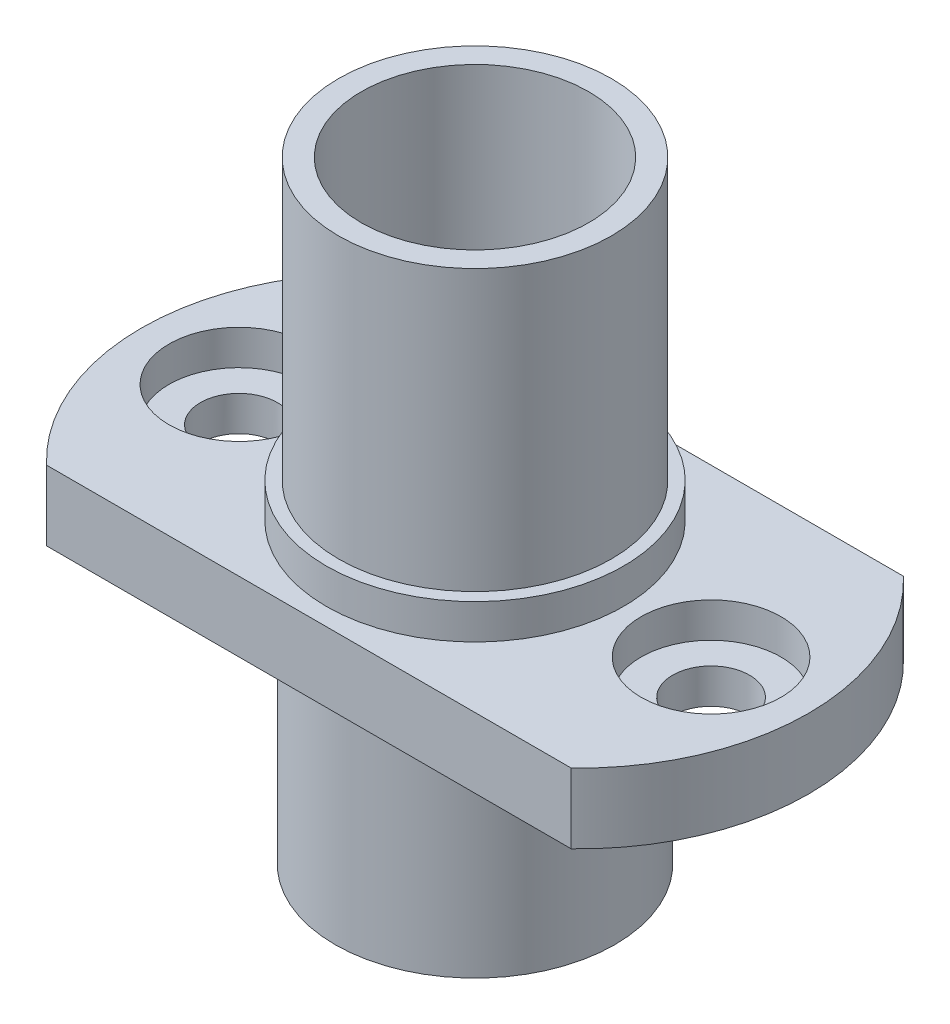
SolidWorks part; units mm, degrees
ref_plane "前视基准面" through (0, 0, 0) normal (0, 0, 1) x (1, 0, 0)
ref_plane "上视基准面" through (0, 0, 0) normal (0, 1, 0) x (1, 0, 0)
ref_plane "右视基准面" through (0, 0, 0) normal (1, 0, 0) x (0, 0, -1)
sketch "草图1" plane through (0, 0, 0) normal (0, 1, 0) x (1, 0, 0)
  line L0 (0, 14.3323) -> (0, -15.2472) construction
  line L1 (-15.1496, 0) -> (19.0046, 0) construction
  line L3 (-7.5, 4.75) -> (7.5, 4.75)
  line L5 (-7.5, -4.75) -> (7.5, -4.75)
  arc A0 (-7.5, -4.75) -> (-7.5, 4.75) centre (-2.99, 0) cw
  arc A1 (7.5, -4.75) -> (7.5, 4.75) centre (2.99, 0) ccw
  dimension "D3" = 6.55
  dimension "D1" = 15
  dimension "D2" = 9.5
extrude "拉伸1" add sketch "草图1" along normal blind 1 and the other way blind 1
sketch "草图2" plane through (0, 1, 0) normal (0, 1, 0) x (-1, 0, 0)
  circle A0 centre (0, 0) radius 4.25
  circle A1 centre (0, 0) radius 3.25
  dimension "D1" = 8.5
  dimension "D2" = 1
extrude "拉伸2" add sketch "草图2" along normal blind 9
sketch "草图3" plane through (0, 1, 0) normal (0, 1, 0) x (-1, 0, 0)
  line L0 (-10.3293, 0) -> (10.9867, 0) construction
  line L1 (0, -7.1957) -> (0, 6.685) construction
  circle A0 centre (-6.75, 0) radius 1.1
  circle A1 centre (6.75, 0) radius 1.1
  dimension "D1" = 13.5
  dimension "D2" = 2.2
extrude "切除-拉伸1" cut sketch "草图3" against normal through all
sketch "草图8" plane through (0, 1, 0) normal (0, 1, 0) x (1, 0, 0)
  circle A0 centre (-6.75, 0) radius 2
  circle A1 centre (6.75, 0) radius 2
  dimension "D1" = 4
  dimension "D2" = 4
extrude "切除-拉伸3" cut sketch "草图8" against normal blind 1
sketch "草图4" plane through (0, -1, 0) normal (0, -1, 0) x (1, 0, 0)
  circle A0 centre (0, 0) radius 4
  dimension "D1" = 8
extrude "凸台-拉伸1" add sketch "草图4" along normal blind 6.5
sketch "草图5" plane through (0, 10, 0) normal (0, 1, 0) x (1, 0, 0)
  circle A0 centre (0, 0) radius 3.9
  dimension "D1" = 7.8
extrude "切除-拉伸2" cut sketch "草图5" against normal offset from surface (8 mm away) 1 flip side to cut up to face at (-6.75, 1, 2)
sketch "草图6" plane through (0, -7.5, 0) normal (0, -1, 0) x (1, 0, 0)
  circle A0 centre (0, 0) radius 0.2
  circle A1 centre (-1.05, 0.1997) radius 0.2
  circle A2 centre (0.756, 0.3) radius 0.2
  dimension "D1" = 0.4
  dimension "D2" = 0.4
  dimension "D3" = 0.4
extrude "凸台-拉伸2" [suppressed] add sketch "草图6" along normal blind 13
sketch "草图7" plane through (0, 0, 0) normal (0, 0, 1) x (1, 0, 0)
  line L0 (0, 0) -> (8.9791, -5.1841) construction
  line L1 (-14.7947, 0) -> (17.5355, 0) construction
  dimension "D1" = 30
ref_plane "基准面1" through (0, 0, 0) normal (-0.5, -0.866, 0) x (0, 0, 1)
